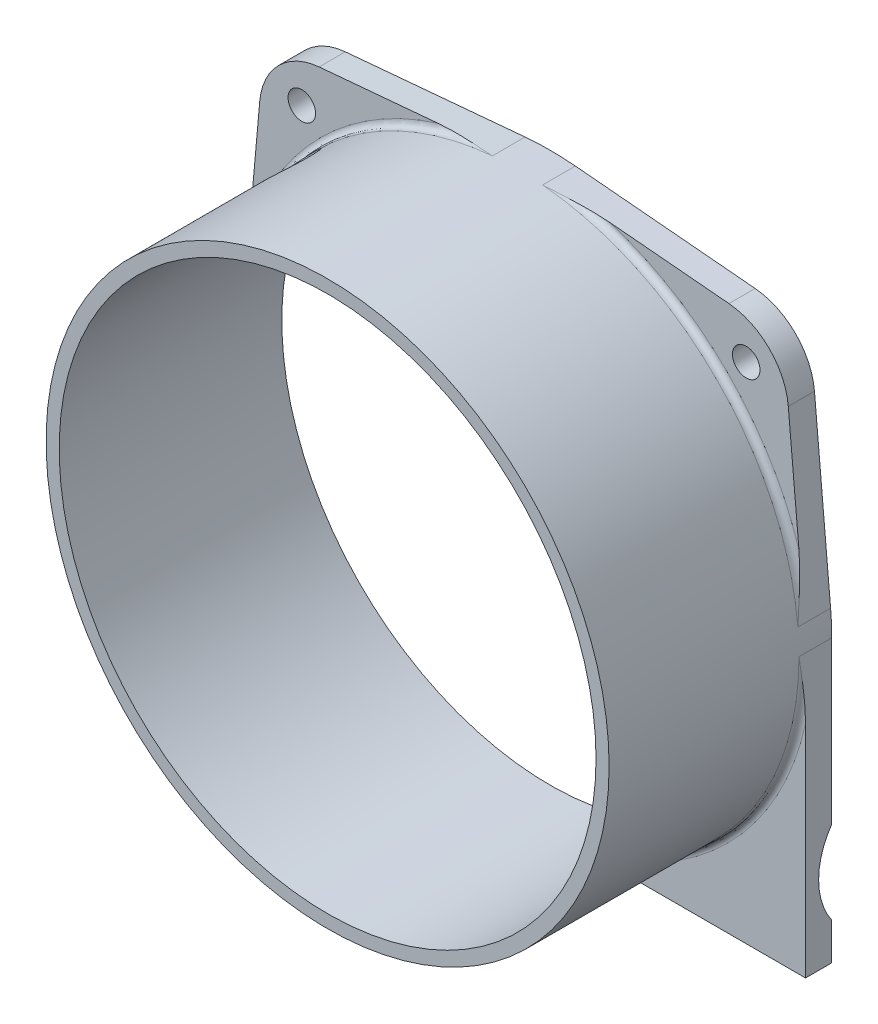
SolidWorks part; units mm, degrees
material "ABS"
ref_plane "Front Plane" through (0, 0, 0) normal (0, 0, 1) x (1, 0, 0)
ref_plane "Top Plane" through (0, 0, 0) normal (0, 1, 0) x (1, 0, 0)
ref_plane "Right Plane" through (0, 0, 0) normal (1, 0, 0) x (0, 0, -1)
sketch "Sketch1" plane through (0, 0, 0) normal (0, 0, 1) x (1, 0, 0)
  line L22 (43, -17.7712) -> (43, 0)
  line L23 (42.8281, 3.8409) -> (40.3656, 31.2988)
  line L24 (31.2988, 40.3656) -> (3.8409, 42.8281)
  line L25 (-3.8409, 42.8281) -> (-31.2988, 40.3656)
  line L26 (-40.3656, 31.2988) -> (-42.8281, 3.8409)
  line L27 (-42.8281, -3.8409) -> (-40.3656, -31.2988)
  line L28 (-31.2988, -40.3656) -> (-3.8409, -42.8281)
  line L29 (0, -43) -> (43.2679, -43)
  line L30 (43, -37.3246) -> (41, -37.3246)
  line L32 (41, -37.3246) -> (41, -41)
  line L33 (41, -41) -> (0, -41)
  line L34 (36.0832, -21) -> (41, -21)
  line L35 (41, -21) -> (41, -24.6754)
  line L36 (41, -24.6754) -> (43, -24.6754)
  line L37 (43, -17.7712) -> (43, 0)
  line L38 (42.8281, 3.8409) -> (40.3656, 31.2988)
  line L39 (31.2988, 40.3656) -> (3.8409, 42.8281)
  line L40 (-3.8409, 42.8281) -> (-31.2988, 40.3656)
  line L41 (-40.3656, 31.2988) -> (-42.8281, 3.8409)
  line L42 (-42.8281, -3.8409) -> (-40.3656, -31.2988)
  line L43 (-31.2988, -40.3656) -> (-3.8409, -42.8281)
  line L44 (0, -43) -> (43, -43)
  line L77 (43, -20.2762) -> (45, -20.2762)
  line L80 (43, -24.6754) -> (43, -20.2762)
  line L82 (45, -41.7238) -> (43, -41.7238)
  line L234 (43, -41.7238) -> (43, -37.3246)
  line L235 (43, -43) -> (43, -24.6754)
  line L292 (43, -24.6754) -> (43, -17.7712)
  arc A2 (35.6485, -20.253) -> (0, -41) centre (0, 0) ccw construction
  arc A3 (40.9385, 2.2457) -> (0, -41) centre (0, 0) ccw construction
  circle A4 centre (0, 0) radius 41
  arc A5 (40.9385, 2.2457) -> (0, -41) centre (0, 0) ccw
  circle A6 centre (-33.9411, -33.9411) radius 2.1 construction
  circle A7 centre (33.9411, 33.9411) radius 2.1 construction
  circle A8 centre (-33.9411, 33.9411) radius 2.1 construction
  circle A9 centre (-33.9411, -33.9411) radius 2.1
  circle A10 centre (33.9411, 33.9411) radius 2.1
  circle A11 centre (-33.9411, 33.9411) radius 2.1
  arc A15 (43, 0) -> (42.8281, 3.8409) centre (0, 0) ccw
  arc A16 (40.3656, 31.2988) -> (31.2988, 40.3656) centre (30.4056, 30.4056) ccw
  arc A17 (3.8409, 42.8281) -> (-3.8409, 42.8281) centre (0, 0) ccw
  arc A18 (-31.2988, 40.3656) -> (-40.3656, 31.2988) centre (-30.4056, 30.4056) ccw
  arc A19 (-42.8281, 3.8409) -> (-42.8281, -3.8409) centre (0, 0) ccw
  arc A20 (-40.3656, -31.2988) -> (-31.2988, -40.3656) centre (-30.4056, -30.4056) ccw
  arc A21 (-3.8409, -42.8281) -> (0, -43) centre (0, 0) ccw
  arc A22 (35.6485, -20.253) -> (0, -41) centre (0, 0) ccw
  arc A23 (35.6485, -20.253) -> (36.0832, -21) centre (36.0832, -20.5) ccw
  arc A24 (43, 0) -> (42.8281, 3.8409) centre (0, 0) ccw
  arc A25 (40.3656, 31.2988) -> (31.2988, 40.3656) centre (30.4056, 30.4056) ccw
  arc A26 (3.8409, 42.8281) -> (-3.8409, 42.8281) centre (0, 0) ccw
  arc A27 (-31.2988, 40.3656) -> (-40.3656, 31.2988) centre (-30.4056, 30.4056) ccw
  arc A28 (-42.8281, 3.8409) -> (-42.8281, -3.8409) centre (0, 0) ccw
  arc A29 (-40.3656, -31.2988) -> (-31.2988, -40.3656) centre (-30.4056, -30.4056) ccw
  arc A30 (-3.8409, -42.8281) -> (0, -43) centre (0, 0) ccw
  arc A31 (35.6485, -20.253) -> (0, -41) centre (0, 0) ccw
  spline S4 degree 3 poles (256.6376, 957.0711) (83.3726, 74.5547) (54.6953, -23.1616) (44.4222, -20.1722) (44.2853, -20.1109) (44.0327, -19.9595) (43.914, -19.8676) (43.7009, -19.6647) (43.6053, -19.5535) (43.4334, -19.3136) (43.3576, -19.1852) (43.2287, -18.9209) (43.1748, -18.7838) (35.7464, 5.3329) (340.0621, 78.5313) (1037.5106, -122.3783) knots -8.816582 -8.816582 -8.816582 -8.816582 0.125 0.125 0.25 0.25 0.375 0.375 0.5 0.5 0.625 0.625 0.75 0.75 21.887228 21.887228 21.887228 21.887228 only from (45, -20.2762) to (43, -17.7712)
  spline S6 degree 3 poles (-815.139, 469.9679) (175.733, -173.2809) (32.9799, -56.4982) (43.6709, -42.3648) (43.8039, -42.2255) (44.0993, -41.9915) (44.2659, -41.8937) (51.9364, -38.9987) (82.6988, -90.2291) (-706.8375, -701.0454) knots -23.028688 -23.028688 -23.028688 -23.028688 0.25 0.25 0.5 0.5 0.75 0.75 11.359512 11.359512 11.359512 11.359512 only from (43.2679, -43) to (45, -41.7238)
  point P0 (43, -24.3388)
  point P1 (0, -41)
  dimension "D1" = 0
extrude "Extrude1" add sketch "Sketch1" along normal blind 4
sketch "Sketch13" plane through (0, 0, 4) normal (0, 0, 1) x (1, 0, 0)
  circle A0 centre (0, 0) radius 41 construction
  circle A1 centre (0, 0) radius 41
  arc A2 (3.8409, 42.8281) -> (-3.8409, 42.8281) centre (0, 0) ccw construction
  circle A3 centre (0, 0) radius 43
  point P3 (-30.646, 27.2364)
  point P8 (4.3397, 42.7834)
extrude "Boss-Extrude2" add sketch "Sketch13" along normal blind 30
sketch "Sketch10" plane through (-1.7678, 1.7678, 0) normal (-0.7071, 0.7071, 0) x (0, 0, 1)
  circle A0 centre (9.5, 0) radius 4
  dimension "D1" = 8
extrude "Cut-Extrude5" cut sketch "Sketch10" along normal blind 55
sketch "Sketch15" plane through (43, 0, 0) normal (1, 0, 0) x (0, 0, -1)
  circle A0 centre (9, -31) radius 11
  dimension "D1" = 22
extrude "Cut-Extrude7" cut sketch "Sketch15" against normal blind 7
fillet "Fillet1" radius 1 4 edges at (30.4056, 30.4056, 4) (-30.4056, 30.4056, 4) (-30.4056, -30.4056, 4) (30.4056, -30.4056, 4)
